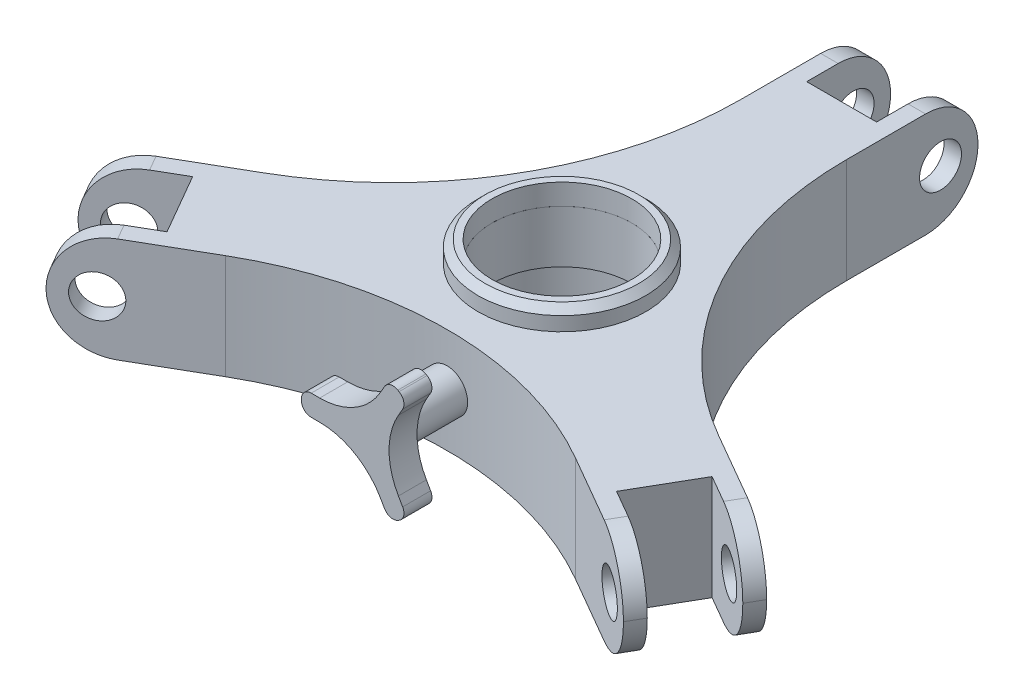
SolidWorks part; units mm, degrees
material "BUTYL"
ref_plane "Plan de face" through (0, 0, 0) normal (0, 0, 1) x (1, 0, 0)
ref_plane "Plan de dessus" through (0, 0, 0) normal (0, 1, 0) x (1, 0, 0)
ref_plane "Plan de droite" through (0, 0, 0) normal (1, 0, 0) x (0, 0, -1)
sketch "Esquisse1" plane through (0, 0, 0) normal (0, 0, 1) x (1, 0, 0)
  line L0 (0, 0) -> (0, 6.9688) construction
  line L1 (-12, 0) -> (-12, 7.5)
  line L2 (-12, 7.5) -> (-10, 7.5)
  line L3 (-10, 7.5) -> (-10, 15)
  line L4 (-10, 15) -> (-15, 15)
  line L5 (-15, 15) -> (-15, 0)
  line L6 (-15, 0) -> (-12, 0)
  dimension "D1" = 2
  dimension "D2" = 3
  dimension "D3" = 15
  dimension "D4" = 7.5
  dimension "D5" = 24
revolve "Révolution1" add sketch "Esquisse1" angle 360 about L0
sketch "Esquisse2" plane through (0, 15, 0) normal (0, 1, 0) x (1, 0, 0)
  line L0 (0, 15) -> (0, 19.143) construction
  line L1 (-7.5, 33.1976) -> (-7.5, 52)
  line L2 (-7.5, 52) -> (7.5, 52)
  line L3 (7.5, 52) -> (7.5, 33.1976)
  line L4 (41.2833, -32.4952) -> (25, -23.094)
  line L5 (48.7833, -19.5048) -> (41.2833, -32.4952)
  line L6 (32.5, -10.1036) -> (48.7833, -19.5048)
  line L7 (-48.7833, -19.5048) -> (-32.5, -10.1036)
  line L8 (-41.2833, -32.4952) -> (-48.7833, -19.5048)
  line L9 (-25, -23.094) -> (-41.2833, -32.4952)
  arc A0 (-10.5, 10.7121) -> (-14.527, 3.7372) centre (0, 0) ccw
  arc A1 (-25, -23.094) -> (25, -23.094) centre (0, -66.3953) cw
  arc A2 (14.527, 3.7372) -> (10.5, 10.7121) centre (0, 0) ccw
  arc A3 (-4.027, -14.4493) -> (4.027, -14.4493) centre (0, 0) ccw
  circle A10 centre (0, 0) radius 15
  arc A11 (-32.5, -10.1036) -> (-7.5, 33.1976) centre (-57.5, 33.1976) ccw
  arc A12 (32.5, -10.1036) -> (7.5, 33.1976) centre (57.5, 33.1976) cw
  point P22 (0, 0)
  dimension "D3" = 52
  dimension "D6" = 15
  dimension "D7" = 50
  dimension "D1" = 15
  dimension "D2" = 7.5
  dimension "D4" = 3
extrude "Boss.-Extru.1" add sketch "Esquisse2" against normal up to surface (15 mm away)
fillet "Congé1" radius 7.5 6 edges at (0, 0, -52) (0, 15, -52) (45.0333, 0, 26) (45.0333, 15, 26) (-45.0333, 0, 26) (-45.0333, 15, 26)
sketch "Esquisse3" plane through (0, 15, 0) normal (0, 1, 0) x (1, 0, 0)
  line L0 (7.5, 44.5) -> (7.5, 33.1976) construction
  line L1 (5, 40) -> (-5, 40)
  line L2 (5, 40) -> (5, 82.1476)
  line L3 (5, 82.1476) -> (-5, 82.1476)
  line L4 (-5, 40) -> (-5, 82.1476)
  line L5 (5, 40) -> (-5, 82.1476) construction
  line L6 (5, 82.1476) -> (-5, 40) construction
  line L8 (-7.5, 52) -> (7.5, 52) construction
  line L9 (32.141, -24.3301) -> (37.141, -15.6699)
  line L10 (32.141, -24.3301) -> (68.6419, -45.4039)
  line L11 (68.6419, -45.4039) -> (73.6419, -36.7437)
  line L12 (37.141, -15.6699) -> (73.6419, -36.7437)
  line L13 (-37.141, -15.6699) -> (-32.141, -24.3301)
  line L14 (-37.141, -15.6699) -> (-73.6419, -36.7437)
  line L15 (-73.6419, -36.7437) -> (-68.6419, -45.4039)
  line L16 (-32.141, -24.3301) -> (-68.6419, -45.4039)
  point P0 (0, 61.0738)
  point P21 (0, 0)
  dimension "D1" = 2.5
  dimension "D2" = 2.5
  dimension "D3" = 12
  dimension "D4" = 3
extrude "Enlèv. mat.-Extru.1" cut sketch "Esquisse3" against normal up to next
sketch "Esquisse4" plane through (7.5, 0, 0) normal (1, 0, 0) x (0, 0, -1)
  line L0 (33.1976, 0) -> (44.5, 0) construction
  circle A0 centre (46.641, 7.5) radius 3
  dimension "D1" = 6
  dimension "D2" = 7.5
  dimension "D3" = 7.5
extrude "Enlèv. mat.-Extru.2" cut sketch "Esquisse4" against normal through all
pattern_circular "Répétition circulaire5" count 3 over 360 of "Enlèv. mat.-Extru.2"
sketch "Esquisse5" plane through (0, 0, 0) normal (0, 0, 1) x (1, 0, 0)
  line L0 (0, 0) -> (0, 15) construction
  line L6 (25, 15) -> (-25, 15) construction
  circle A0 centre (0, 7.5) radius 3
  dimension "D1" = 6
extrude "Boss.-Extru.2" add sketch "Esquisse5" along normal blind 24
sketch "Esquisse6" plane through (0, 15, 0) normal (0, 1, 0) x (1, 0, 0)
  circle A0 centre (0, 0) radius 10
extrude "Enlèv. mat.-Extru.3" cut sketch "Esquisse6" against normal blind 24
sketch "Esquisse7" plane through (0, 0, 0) normal (0, -1, 0) x (1, 0, 0)
  circle A0 centre (0, 0) radius 12
extrude "Enlèv. mat.-Extru.5" cut sketch "Esquisse7" against normal up to surface (7.5 mm away) up to face at (0, 7.5, -0.2104)
sketch "Esquisse8" plane through (0, 0, 24) normal (0, 0, 1) x (1, 0, 0)
  line L0 (-3, 7.5) -> (-15.5068, 7.5) construction
  line L1 (-6.6395, 6) -> (-7.8534, 6)
  line L2 (-9.2534, 7.4) -> (-9.2534, 7.6)
  line L3 (-7.8534, 9) -> (-6.6395, 9)
  line L4 (2.0207, 14) -> (2.6277, 15.0512)
  line L5 (4.5401, 15.5637) -> (4.7133, 15.4637)
  line L6 (5.2257, 13.5512) -> (4.6188, 12.5)
  line L7 (4.6188, 2.5) -> (5.2257, 1.4488)
  line L8 (4.7133, -0.4637) -> (4.5401, -0.5637)
  line L9 (2.6277, -0.0512) -> (2.0207, 1)
  circle A0 centre (0, 7.5) radius 3 construction
  circle A1 centre (0, 7.5) radius 3 construction
  arc A3 (-6.6395, 6) -> (2.0207, 1) centre (-6.6395, -4) cw
  arc A4 (4.6188, 12.5) -> (4.6188, 2.5) centre (13.2791, 7.5) ccw
  arc A5 (2.0207, 14) -> (-6.6395, 9) centre (-6.6395, 19) cw
  arc A6 (-7.8534, 6) -> (-9.2534, 7.4) centre (-7.8534, 7.4) cw
  arc A7 (-9.2534, 7.6) -> (-7.8534, 9) centre (-7.8534, 7.6) cw
  arc A8 (4.5401, 15.5637) -> (2.6277, 15.0512) centre (3.8401, 14.3512) ccw
  arc A9 (4.7133, 15.4637) -> (5.2257, 13.5512) centre (4.0133, 14.2512) cw
  arc A10 (5.2257, 1.4488) -> (4.7133, -0.4637) centre (4.0133, 0.7488) cw
  arc A11 (4.5401, -0.5637) -> (2.6277, -0.0512) centre (3.8401, 0.6488) cw
  circle A12 centre (0, 7.5) radius 3
  point P8 (-9.2534, 7.5)
  point P25 (0, 7.5)
  point P28 (-9.2534, 6)
  point P31 (-9.2534, 9)
  dimension "D3" = 10
  dimension "D4" = 1.4
  dimension "D1" = 3
  dimension "D2" = 3
extrude "Boss.-Extru.3" add sketch "Esquisse8" along normal blind 4 separate body
sketch "Esquisse10" plane through (0, 15, 0) normal (0, 1, 0) x (1, 0, 0)
  circle A0 centre (0, 0) radius 12
  circle A1 centre (0, 0) radius 10
  dimension "D1" = 2
extrude "Boss.-Extru.5" add sketch "Esquisse10" along normal blind 3
chamfer "Chanfrein1" distance 1 angle 45 1 edges at (0, 18, 12)
